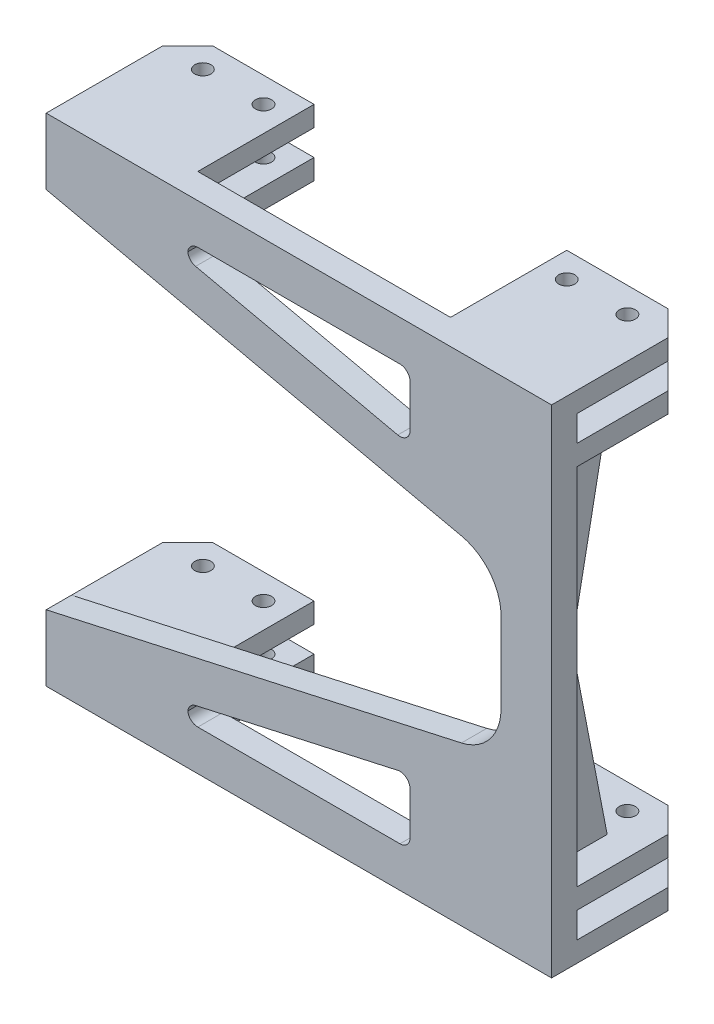
SolidWorks part; units mm, degrees
ref_plane "前视基准面" through (0, 0, 0) normal (0, 0, 1) x (1, 0, 0)
ref_plane "上视基准面" through (0, 0, 0) normal (0, 1, 0) x (1, 0, 0)
ref_plane "右视基准面" through (0, 0, 0) normal (1, 0, 0) x (0, 0, -1)
sketch "草图1" plane through (0, 0, 0) normal (0, 0, 1) x (1, 0, 0)
  line L0 (-158.1257, 0) -> (-266.6901, 0) construction
  line L1 (-260.8862, 4.1) -> (-160.8862, 4.1)
  line L2 (-260.8862, 4.1) -> (-260.8862, -94.1)
  line L3 (-260.8862, -94.1) -> (-160.8862, -94.1)
  line L4 (-160.8862, 4.1) -> (-160.8862, -94.1)
  line L5 (-158.1257, -90) -> (-266.6901, -90) construction
  line L6 (-245.1311, -22.3584) -> (-221.6706, -76.813)
  line L7 (-235.4386, -9) -> (-205.9533, -9)
  line L8 (-250.8862, -23.5454) -> (-250.8862, -78)
  line L9 (-247.8862, -81) -> (-224.4257, -81)
  line L10 (-170.8862, -12) -> (-170.8862, -41.4233)
  line L11 (-203.0405, -12.7178) -> (-213.7689, -56.2546)
  line L12 (-219.4369, -56.7238) -> (-238.1938, -13.187)
  line L13 (-235.4386, -9) -> (-212.1706, -9)
  line L15 (-208.1237, -77.2796) -> (-197.3201, -33.6026)
  line L16 (-191.6557, -33.1289) -> (-172.7059, -76.806)
  line L17 (-158.1257, -5) -> (-266.6901, -5) construction
  line L18 (-158.1257, -85) -> (-266.6901, -85) construction
  line L19 (-176.6384, -42.6174) -> (-189.404, -13.194)
  line L20 (-186.6519, -9) -> (-173.8862, -9)
  line L21 (-205.2115, -81) -> (-175.458, -81)
  arc A0 (-173.8862, -9) -> (-170.8862, -12) centre (-173.8862, -12) cw
  arc A1 (-189.404, -13.194) -> (-186.6519, -9) centre (-186.6519, -12) cw
  arc A2 (-176.6384, -42.6174) -> (-170.8862, -41.4233) centre (-173.8862, -41.4233) ccw
  arc A3 (-172.7059, -76.806) -> (-175.458, -81) centre (-175.458, -78) cw
  arc A4 (-208.1237, -77.2796) -> (-205.2115, -81) centre (-205.2115, -78) ccw
  arc A5 (-191.6557, -33.1289) -> (-197.3201, -33.6026) centre (-194.4078, -34.323) ccw
  arc A6 (-203.0405, -12.7178) -> (-205.9533, -9) centre (-205.9533, -12) ccw
  arc A7 (-238.1938, -13.187) -> (-235.4386, -9) centre (-235.4386, -12) cw
  arc A8 (-213.7689, -56.2546) -> (-219.4369, -56.7238) centre (-216.6817, -55.5368) cw
  arc A9 (-221.6706, -76.813) -> (-224.4257, -81) centre (-224.4257, -78) cw
  arc A10 (-250.8862, -78) -> (-247.8862, -81) centre (-247.8862, -78) ccw
  arc A11 (-245.1311, -22.3584) -> (-250.8862, -23.5454) centre (-247.8862, -23.5454) ccw
  point P33 (-191.2237, -9)
  point P40 (-209.044, -81)
  dimension "D8" = 3
  dimension "D1" = 100
  dimension "D2" = 4.1
  dimension "D3" = 4.1
  dimension "D4" = 4
  dimension "D5" = 10
  dimension "D6" = 4
  dimension "D7" = 10
  dimension "D9" = 10
  dimension "D10" = 10
extrude "凸台-拉伸1" add sketch "草图1" along normal blind 5 contours L4 L1 L2 L3 A11 L6 A9 L9 A10 L8 A5 L16 A3 L21 A4 L15 A2 L19 A1 L20 A0 L10 L11 A8 L12 A7 L7 A6
sketch "草图2" plane through (0, 0, 0) normal (0, 0, -1) x (-1, 0, 0)
  line L0 (260.8862, 4.1) -> (260.8862, -94.1) construction
  line L1 (260.8862, 4.1) -> (235.8862, 4.1)
  line L2 (260.8862, 4.1) -> (260.8862, 0.1)
  line L3 (260.8862, 0.1) -> (235.8862, 0.1)
  line L4 (235.8862, 4.1) -> (235.8862, 0.1)
  line L5 (260.8862, -9) -> (235.8862, -9)
  line L6 (260.8862, -9) -> (260.8862, -5)
  line L7 (260.8862, -5) -> (235.8862, -5)
  line L8 (235.8862, -9) -> (235.8862, -5)
  line L9 (210.8862, 4.1) -> (210.8862, -94.1) construction
  line L10 (260.8862, 4.1) -> (160.8862, 4.1) construction
  line L11 (260.8862, -94.1) -> (160.8862, -94.1) construction
  line L12 (260.8862, -45) -> (160.8862, -45) construction
  line L13 (160.8862, 4.1) -> (160.8862, -94.1) construction
  line L14 (185.8862, -9) -> (185.8862, -5)
  line L15 (160.8862, -5) -> (185.8862, -5)
  line L16 (160.8862, -9) -> (160.8862, -5)
  line L17 (160.8862, -9) -> (185.8862, -9)
  line L18 (185.8862, 4.1) -> (185.8862, 0.1)
  line L19 (160.8862, 0.1) -> (185.8862, 0.1)
  line L20 (160.8862, 4.1) -> (160.8862, 0.1)
  line L21 (160.8862, 4.1) -> (185.8862, 4.1)
  line L22 (160.8862, -94.1) -> (185.8862, -94.1)
  line L23 (160.8862, -94.1) -> (160.8862, -90.1)
  line L24 (160.8862, -90.1) -> (185.8862, -90.1)
  line L25 (185.8862, -94.1) -> (185.8862, -90.1)
  line L26 (160.8862, -81) -> (185.8862, -81)
  line L27 (160.8862, -81) -> (160.8862, -85)
  line L28 (160.8862, -85) -> (185.8862, -85)
  line L29 (185.8862, -81) -> (185.8862, -85)
  line L30 (235.8862, -81) -> (235.8862, -85)
  line L31 (260.8862, -85) -> (235.8862, -85)
  line L32 (260.8862, -81) -> (260.8862, -85)
  line L33 (260.8862, -81) -> (235.8862, -81)
  line L34 (235.8862, -94.1) -> (235.8862, -90.1)
  line L35 (260.8862, -90.1) -> (235.8862, -90.1)
  line L36 (260.8862, -94.1) -> (260.8862, -90.1)
  line L37 (260.8862, -94.1) -> (235.8862, -94.1)
  dimension "D1" = 4
  dimension "D2" = 5.1
  dimension "D3" = 25
  dimension "D4" = 25
  dimension "D5" = 4
extrude "凸台-拉伸2" add sketch "草图2" along normal blind 23
chamfer "倒角1" distance 5 angle 45 8 edges at (-260.8862, -92.1, -23) (-260.8862, -83, -23) (-160.8862, -83, -23) (-160.8862, -92.1, -23) (-160.8862, -7, -23) (-160.8862, 2.1, -23) (-260.8862, -7, -23) (-260.8862, 2.1, -23)
sketch "草图3" plane through (0, 4.1, 0) normal (0, 1, 0) x (1, 0, 0)
  line L0 (-255.8862, 23) -> (-235.8862, 23) construction
  line L1 (-185.8862, 23) -> (-165.8862, 23) construction
  line L2 (-235.8862, 23) -> (-235.8862, 0) construction
  line L4 (-185.8862, 23) -> (-185.8862, 0) construction
  circle A0 centre (-252.8862, 18) radius 1.6
  circle A1 centre (-240.8862, 18) radius 1.6
  circle A2 centre (-180.8862, 18) radius 1.6
  circle A3 centre (-168.8862, 18) radius 1.6
  dimension "D1" = 3.2
  dimension "D2" = 5
  dimension "D3" = 5
  dimension "D4" = 5
  dimension "D5" = 5
  dimension "D6" = 5
  dimension "D7" = 12
  dimension "D8" = 5
  dimension "D9" = 12
extrude "切除-拉伸1" cut sketch "草图3" against normal blind 100
sketch "草图5" plane through (0, 0, 0) normal (0, 0, -1) x (-1, 0, 0)
  line L0 (185.8862, -81) -> (165.8862, -81) construction
  line L1 (260.8862, -9) -> (170.8862, -9)
  line L2 (260.8862, -9) -> (260.8862, -81)
  line L3 (260.8862, -81) -> (170.8862, -81)
  line L4 (170.8862, -9) -> (170.8862, -81)
  line L5 (160.8862, -9) -> (160.8862, -81) construction
  dimension "D1" = 10
extrude "切除-拉伸2" cut sketch "草图5" against normal blind 10
sketch "草图6" plane through (0, 0, 0) normal (0, 0, -1) x (-1, 0, 0)
  line L1 (260.8862, -9) -> (170.8862, -9)
  line L2 (170.8862, -9) -> (170.8862, -29)
  line L3 (170.8862, -81) -> (260.8862, -81)
  line L4 (170.8862, -29) -> (260.8862, -9)
  line L5 (170.8862, -61) -> (260.8862, -81)
  line L6 (170.8862, -61) -> (170.8862, -81)
  dimension "D1" = 20
  dimension "D2" = 20
extrude "凸台-拉伸3" add sketch "草图6" against normal up to vertex (5 mm away)
fillet "圆角1" radius 10 2 edges at (-170.8862, -29, 2.5) (-170.8862, -61, 2.5)
ref_plane "基准面1" through (-170.8862, 0, 0) normal (1, 0, 0) x (0, 0, -1)
sketch "草图7" plane through (-170.8862, 0, 0) normal (1, 0, 0) x (0, 0, -1)
  line L0 (12, -9) -> (5, -45)
  line L1 (5, -45) -> (12, -81)
  line L3 (-5, -45) -> (5, -45) construction
  line L4 (-5, 4.1) -> (-5, -94.1) construction
  line L5 (12, -9) -> (0, -9)
  line L6 (0, -9) -> (0, -81)
  line L7 (0, -81) -> (12, -81)
  dimension "D1" = 10
  dimension "D2" = 12
  dimension "D3" = 12
extrude "凸台-拉伸4" add sketch "草图7" along normal blind 4
sketch "草图8" plane through (0, 0, 0) normal (0, 0, -1) x (-1, 0, 0)
  line L0 (188.8862, -16.8048) -> (232.8862, -7.0271)
  line L1 (232.8862, -7.0271) -> (232.8862, -3.9)
  line L2 (232.8862, -3.9) -> (188.8862, -3.9)
  line L3 (188.8862, -3.9) -> (188.8862, -16.8048)
  line L4 (160.8862, -45) -> (254.3895, -45) construction
  line L5 (160.8862, -9) -> (160.8862, -81) construction
  line L6 (235.8862, 4.1) -> (185.8862, 4.1) construction
  line L7 (178.7169, -27.2598) -> (260.8862, -9) construction
  line L8 (185.8862, -9) -> (185.8862, -5) construction
  line L9 (235.8862, -5) -> (235.8862, -9) construction
  line L10 (188.8862, -86.1) -> (188.8862, -73.1952)
  line L11 (232.8862, -86.1) -> (188.8862, -86.1)
  line L12 (232.8862, -82.9729) -> (232.8862, -86.1)
  line L13 (188.8862, -73.1952) -> (232.8862, -82.9729)
  point P14 (185.8862, -7)
  point P17 (235.8862, -7)
  dimension "D1" = 8
  dimension "D2" = 8
  dimension "D3" = 3
  dimension "D4" = 3
extrude "切除-拉伸3" cut sketch "草图8" against normal blind 10
fillet "Fillet1" radius 10 1 edges at (-168.8862, -45, -5)
fillet "Fillet2" radius 2 8 edges at (-188.8862, -16.8048, 2.5) (-232.8862, -7.0271, 2.5) (-232.8862, -3.9, 2.5) (-188.8862, -3.9, 2.5) (-188.8862, -73.1952, 2.5) (-232.8862, -86.1, 2.5) (-232.8862, -82.9729, 2.5) (-188.8862, -86.1, 2.5)
